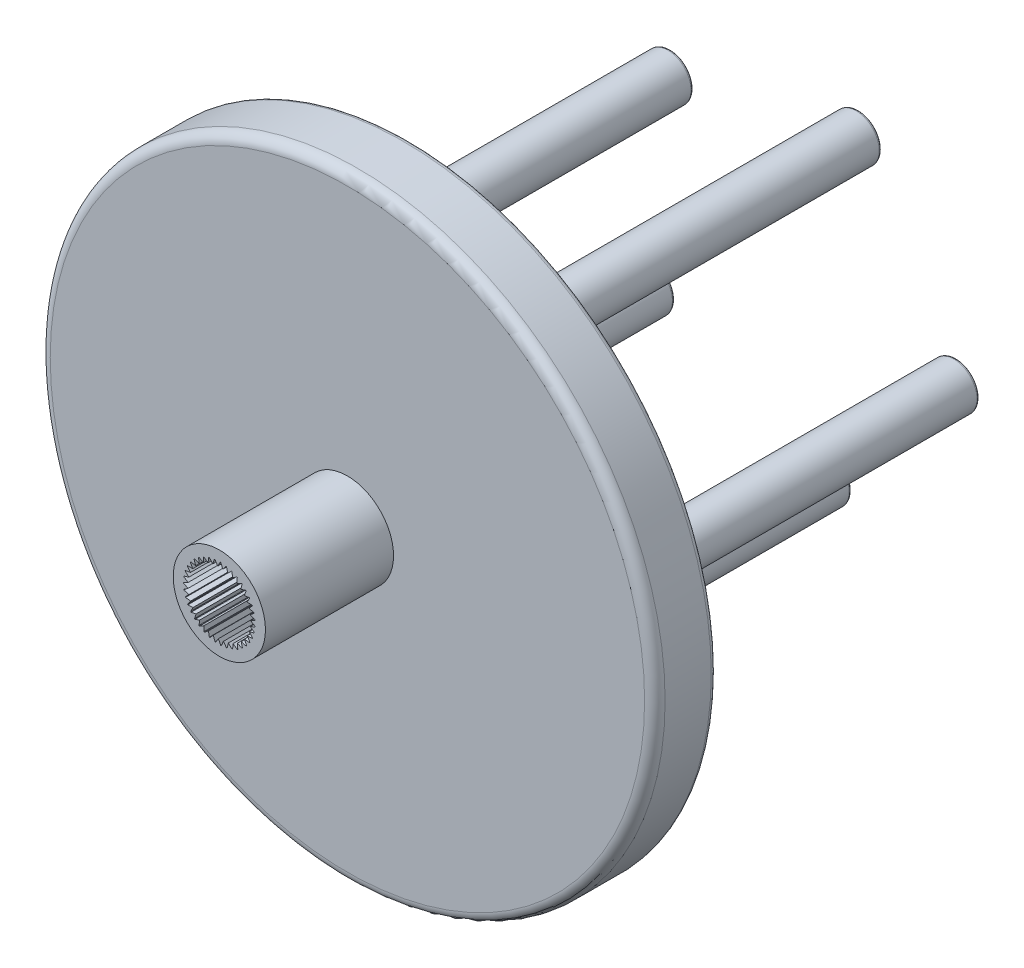
SolidWorks part; units mm, degrees
ref_plane "Front Plane" through (0, 0, 0) normal (0, 0, 1) x (1, 0, 0)
ref_plane "Top Plane" through (0, 0, 0) normal (0, 1, 0) x (1, 0, 0)
ref_plane "Right Plane" through (0, 0, 0) normal (1, 0, 0) x (0, 0, -1)
sketch "Sketch2" plane through (0, 0, 0) normal (0, 0, 1) x (1, 0, 0)
  line L0 (-6.9282, 1) -> (-6.101, 0.438)
  line L1 (-6.101, 0.438) -> (-7, 0)
  circle A0 centre (0, 0) radius 19.5
  circle A1 centre (0, 0) radius 32
  circle A2 centre (0, 0) radius 60
  circle A3 centre (-23.9548, 21.2171) radius 4.5
  circle A4 centre (12.7763, 29.3388) radius 4.5
  circle A5 centre (31.851, -3.0847) radius 4.5
  circle A6 centre (6.9087, -31.2453) radius 4.5
  circle A7 centre (-27.5811, -16.2259) radius 4.5
  circle A8 centre (0, 0) radius 9
  circle A9 centre (0, 0) radius 7
  point P18 (0, 0)
  dimension "D1" = 120
  dimension "D2" = 39
  dimension "D3" = 9
  dimension "D6" = 18
  dimension "D7" = 2
  dimension "D4" = 32
  dimension "D8" = 1
  dimension "D9" = 1
  dimension "D10" = 1
  dimension "D5" = 5
extrude "Boss-Extrude1" add sketch "Sketch2" along normal blind 37 contours L0 A9 L1 | A8 A9 region at (-6.6844, 0.4799, 0) region at (-8.7454, 0, 0)
extrude "Boss-Extrude2" add sketch "Sketch2<4>" against normal blind 75 separate body contours A1 A3 | A1 A3 | A1 A4 | A1 A4 | A1 A7 | A1 A6 | A1 A6 | A1 A5 | A1 A5 | A7 region at (29.8944, -2.8952, 0) region at (33.6941, -3.2632, 0) region at (11.9914, 27.5366, 0) region at (13.5156, 31.0366, 0) region at (7.3085, -33.0534, 0) region at (6.4843, -29.326, 0) region at (-22.4833, 19.9138, 0) region at (-25.341, 22.4449, 0) region at (-25.8869, -15.2292, 0)
sketch "Sketch2<4>" plane through (0, 0, 0) normal (0, 0, 1) x (1, 0, 0) same geometry as "Sketch2"
extrude "Boss-Extrude3" add sketch "Sketch2<6>" along normal blind 12 contours A1 A7 | A1 A7 | A1 A6 | A1 A6 | A1 A3 | A1 A3 | A1 A5 | A1 A4 | A1 A4 | A1 A5 | A0 A8 | A7 A1 A6 A5 A4 A3 A0 | A2 A7 A1 A3 A4 A5 A6 region at (-18.9485, 0, 0) region at (29.8944, -2.8952, 0) region at (33.6941, -3.2632, 0) region at (26.4713, -2.5637, 0) region at (11.9914, 27.5366, 0) region at (13.5156, 31.0366, 0) region at (7.3085, -33.0534, 0) region at (6.4843, -29.326, 0) region at (-22.4833, 19.9138, 0) region at (-25.341, 22.4449, 0) region at (-29.1772, -17.1649, 0) region at (-25.8869, -15.2292, 0) region at (-58.3029, 0, 0)
sketch "Sketch2<6>" plane through (0, 0, 0) normal (0, 0, 1) x (1, 0, 0) same geometry as "Sketch2"
pattern_circular "CirPattern1" count 39 over 360 about axis through (0, 0, 37) along (0, 0, 1) of "Boss-Extrude1"
sketch "Sketch3" plane through (0, 0, 12) normal (0, 0, 1) x (1, 0, 0)
  circle A0 centre (0, 0) radius 19.5
  circle A1 centre (0, 0) radius 17.5
  dimension "D1" = 35
  dimension "D2" = 2
extrude "Boss-Extrude4" add sketch "Sketch3" against normal blind 6 from surface starting at face at (0, 0, 0)
fillet "Fillet2" radius 0.3 2 edges at (17.5, 0, -6) (19.5, 0, -6)
fillet "Fillet3" radius 2 1 edges at (60, 0, 12)
fillet "Fillet4" radius 1 1 edges at (60, 0, 0)
sketch "Sketch4" plane through (0, 0, -75) normal (0, 0, -1) x (-1, 0, 0)
  circle A0 centre (23.9548, 21.2171) radius 3
  circle A1 centre (27.5811, -16.2259) radius 3
  circle A2 centre (-6.9087, -31.2453) radius 3
  circle A3 centre (-31.851, -3.0847) radius 3
  circle A4 centre (-12.7763, 29.3388) radius 3
  point P14 (0, 0)
  dimension "D1" = 5
extrude "Cut-Extrude1" cut sketch "Sketch4" against normal blind 15
fillet "Fillet5" radius 0.5 10 edges at (36.351, -3.0847, -75) (28.851, -3.0847, -75) (11.4087, -31.2453, -75) (3.9087, -31.2453, -75) (-23.0811, -16.2259, -75) (-30.5811, -16.2259, -75) (-19.4548, 21.2171, -75) (-26.9548, 21.2171, -75) (17.2763, 29.3388, -75) (9.7763, 29.3388, -75)
